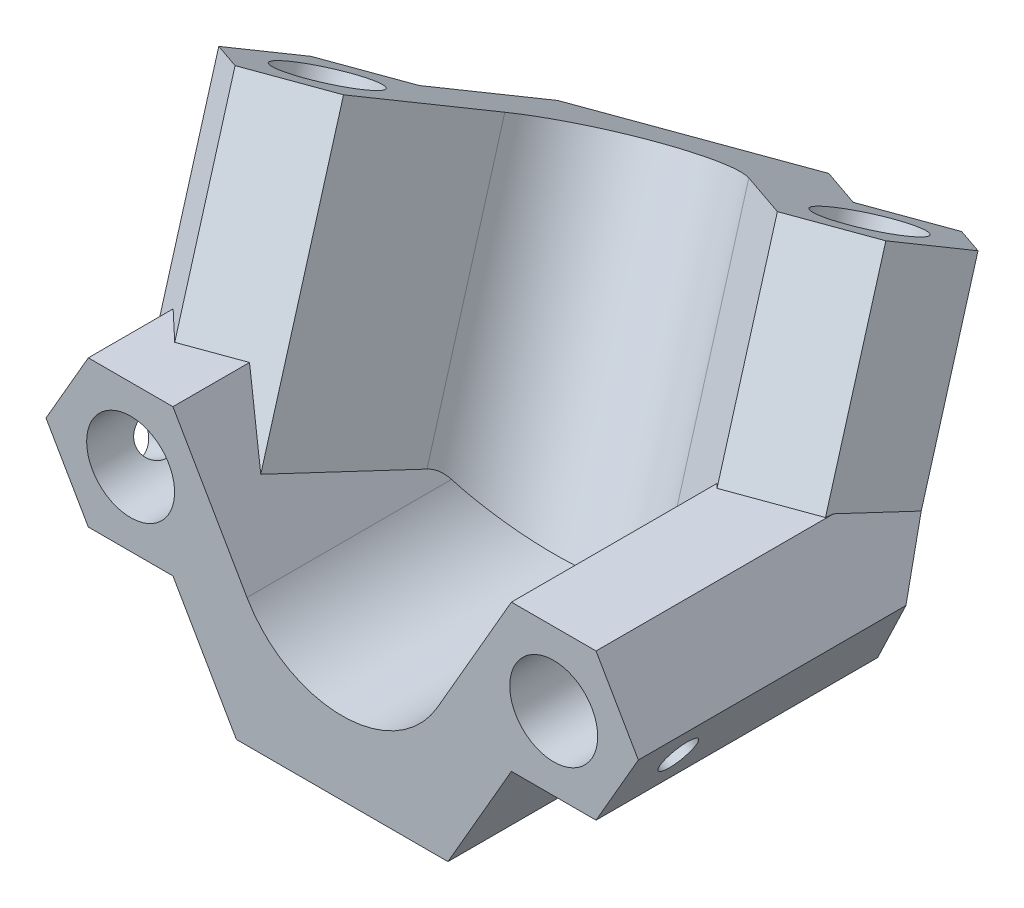
SolidWorks part; units mm, degrees
ref_plane "Front Plane" through (0, 0, 0) normal (0, 0, 1) x (1, 0, 0)
ref_plane "Top Plane" through (0, 0, 0) normal (0, 1, 0) x (1, 0, 0)
ref_plane "Right Plane" through (0, 0, 0) normal (1, 0, 0) x (0, 0, -1)
sketch "Sketch1" plane through (0, 0, 0) normal (0, 1, 0) x (1, 0, 0)
  line L0 (0, 0) -> (0, -10) construction
  line L1 (0, 0) -> (-3.4202, 9.3969) construction
  dimension "D1" = 10
  dimension "D2" = 160
  dimension "D3" = 10
ref_plane "Plane1" through (0, 0, 0) normal (0.9397, 0, -0.342) x (-0.342, 0, -0.9397)
sketch "Sketch2" plane through (0, 0, 0) normal (0.9397, 0, -0.342) x (-0.342, 0, -0.9397)
  line L0 (0, 0) -> (10, 0) construction
  line L1 (0, 0) -> (10, 0) construction
  line L2 (10, 0) -> (10, 17.3205) construction
  line L3 (10, 17.3205) -> (0, 0) construction
  dimension "D1" = 60
  dimension "D2" = 10
sketch "Sketch3" plane through (0, 0, 0) normal (0, 0, 1) x (1, 0, 0)
  line L0 (0, 15) -> (0, -15) construction
  line L1 (13.8564, 6) -> (8.6603, 15) construction
  line L2 (8.6603, 15) -> (0, 15) construction
  line L3 (-8.6603, 15) -> (-13.8564, 6) construction
  line L4 (-13.8564, -6) -> (-8.6603, -15)
  line L5 (-8.6603, -15) -> (8.6603, -15)
  line L6 (8.6603, -15) -> (13.8564, -6)
  line L7 (0, 0) -> (17.3205, 0) construction
  line L8 (13.8564, 6) -> (12.1244, 3) construction
  line L9 (24.2487, 0) -> (20.7846, 6)
  line L10 (20.7846, 6) -> (13.8564, 6)
  line L11 (12.1244, 3) -> (7.7942, -4.5) construction
  line L12 (12.1244, -3) -> (13.8564, -6) construction
  line L13 (13.8564, -6) -> (20.7846, -6)
  line L14 (20.7846, -6) -> (24.2487, 0)
  line L15 (10.3923, 0) -> (12.1244, -3) construction
  line L16 (13.8564, -6) -> (14.3205, -5.1962) construction
  line L17 (15.5205, -3.1177) -> (17.3205, 0) construction
  line L18 (14.3205, -5.1962) -> (15.5205, -3.1177) construction
  line L19 (17.3205, 0) -> (15.5205, 3.1177) construction
  line L20 (15.5205, 3.1177) -> (14.3205, 5.1962) construction
  line L21 (14.3205, 5.1962) -> (13.8564, 6) construction
  line L22 (-13.8564, -6) -> (-20.7846, -6)
  line L23 (-20.7846, -6) -> (-24.2487, 0)
  line L24 (-24.2487, 0) -> (-20.7846, 6)
  line L25 (-20.7846, 6) -> (-13.8564, 6)
  line L26 (-13.8564, 6) -> (-15.5205, 3.1177) construction
  line L27 (-15.5205, 3.1177) -> (-17.3205, 0) construction
  line L28 (-17.3205, 0) -> (-15.5205, -3.1177) construction
  line L29 (-15.5205, -3.1177) -> (-13.8564, -6) construction
  line L30 (-17.3205, 6) -> (-17.3205, -6) construction
  line L31 (-7.7942, -4.5) -> (-13.8564, 6)
  line L32 (7.7942, -4.5) -> (13.8564, 6)
  line L33 (-10.3923, 0) -> (-7.7942, -4.5) construction
  line L34 (0, 15) -> (-8.6603, 15) construction
  line L35 (7.7942, -4.5) -> (10.3923, 0) construction
  line L36 (10.3923, 0) -> (7.7942, -4.5) construction
  circle A0 centre (0, 0) radius 15 construction
  circle A1 centre (17.3205, 0) radius 3.6
  circle A2 centre (17.3205, 0) radius 6 construction
  circle A3 centre (-17.3205, 0) radius 3.6
  arc A4 (-7.7942, -4.5) -> (7.7942, -4.5) centre (0, 0) ccw
  arc A5 (0, 9) -> (-7.7942, -4.5) centre (0, 0) ccw construction
  arc A6 (7.7942, -4.5) -> (0, 9) centre (0, 0) ccw construction
  dimension "D2" = 7.2
  dimension "D4" = 18
  dimension "D1" = 30
  dimension "D3" = 12
extrude "Boss-Extrude1" add sketch "Sketch3" along normal blind 15
ref_plane "Plane2" through (-3.4202, 17.3205, -9.3969) normal (0.171, -0.866, 0.4698) x (-0.9849, -0.1641, 0.056)
sketch "Sketch25" plane through (0, 0, 0) normal (0, 0, -1) x (-1, 0, 0)
  line L0 (-7.7942, -4.5) -> (-13.8564, 6)
  line L1 (-13.8564, 6) -> (-20.7846, 6)
  line L2 (-20.7846, 6) -> (-24.2487, 0)
  line L3 (-24.2487, 0) -> (-20.7846, -6)
  line L4 (-20.7846, -6) -> (-13.8564, -6)
  line L5 (-13.8564, -6) -> (-8.6603, -15)
  line L6 (-8.6603, -15) -> (8.6603, -15)
  line L7 (8.6603, -15) -> (13.8564, -6)
  line L8 (13.8564, -6) -> (20.7846, -6)
  line L9 (20.7846, -6) -> (24.2487, 0)
  line L10 (24.2487, 0) -> (20.7846, 6)
  line L11 (20.7846, 6) -> (13.8564, 6)
  line L12 (13.8564, 6) -> (7.7942, -4.5)
  arc A0 (-7.7942, -4.5) -> (7.7942, -4.5) centre (0, 0) ccw
  arc A1 (-7.7942, -4.5) -> (7.7942, -4.5) centre (0, 0) ccw construction
  arc A2 (7.7942, -4.5) -> (-7.7942, -4.5) centre (0, 0) ccw construction
sketch "Sketch11" plane through (-3.4202, 17.3205, -9.3969) normal (0.171, -0.866, 0.4698) x (-0.9849, -0.1641, 0.056)
  line L0 (-4.9224, -14.1693) -> (4.9224, 14.1693) construction
  line L7 (13.1031, 11.3274) -> (-3.2583, 17.0113)
  line L20 (-3.2583, 17.0113) -> (-11.1201, 10.2148)
  line L21 (-15.058, -1.1206) -> (-13.1031, -11.3274) construction
  line L22 (-4.9224, -14.1693) -> (3.2583, -17.0113) construction
  line L23 (3.2583, -17.0113) -> (11.1201, -10.2148) construction
  line L24 (16.3613, -5.6839) -> (15.7029, -2.2464) construction
  line L25 (2.8419, 8.1807) -> (0, 0) construction
  line L26 (-16.3613, 5.6839) -> (16.3613, -5.6839) construction
  line L27 (15.058, 1.1206) -> (12.4374, -1.1449) construction
  line L28 (-11.1201, 10.2148) -> (-17.6647, 12.4884)
  line L35 (-17.6647, 12.4884) -> (-22.9059, 7.9574)
  line L42 (-22.9059, 7.9574) -> (-21.6026, 1.1529)
  line L43 (-21.6026, 1.1529) -> (-15.058, -1.1206)
  line L44 (-15.058, -1.1206) -> (-5.8859, 6.8085)
  line L45 (-8.8393, -1.6931) -> (-10.4685, 6.8126) construction
  line L46 (22.9059, -7.9574) -> (21.6026, -1.1529)
  line L47 (21.6026, -1.1529) -> (15.058, 1.1206)
  line L48 (5.8859, -6.8085) -> (9.8168, -3.4103) construction
  line L49 (8.8393, 1.6931) -> (11.1201, -10.2148)
  line L50 (11.1201, -10.2148) -> (17.6647, -12.4884)
  line L51 (17.6647, -12.4884) -> (22.9059, -7.9574)
  line L52 (12.4374, -1.1449) -> (5.8859, -6.8085) construction
  line L53 (9.8168, -3.4103) -> (8.8393, 1.6931) construction
  line L54 (15.2326, 0.209) -> (15.058, 1.1206) construction
  line L55 (15.058, 1.1206) -> (13.1031, 11.3274)
  line L56 (15.7029, -2.2464) -> (15.2326, 0.209) construction
  line L57 (13.7136, -7.9728) -> (16.3613, -5.6839) construction
  line L58 (11.8223, -9.6078) -> (13.7136, -7.9728) construction
  line L59 (11.1201, -10.2148) -> (11.8223, -9.6078) construction
  line L60 (-10.4685, 6.8126) -> (-11.1201, 10.2148) construction
  line L61 (-11.8223, 9.6078) -> (-13.6379, 8.0382) construction
  line L62 (-13.6379, 8.0382) -> (-16.3613, 5.6839) construction
  line L63 (-16.3613, 5.6839) -> (-15.6841, 2.1482) construction
  line L64 (-11.1201, 10.2148) -> (-11.8223, 9.6078) construction
  line L65 (-15.6841, 2.1482) -> (-15.2326, -0.209) construction
  line L66 (-15.2326, -0.209) -> (-15.058, -1.1206) construction
  line L67 (-5.8859, 6.8085) -> (-9.8168, 3.4103) construction
  line L68 (-9.8168, 3.4103) -> (-8.8393, -1.6931) construction
  line L69 (-13.1031, -11.3274) -> (-4.9224, -14.1693) construction
  circle A0 centre (0, 0) radius 15 construction
  circle A2 centre (-16.3613, 5.6839) radius 6 construction
  circle A4 centre (-16.3613, 5.6839) radius 3.6
  circle A5 centre (16.3613, -5.6839) radius 6 construction
  circle A6 centre (16.3613, -5.6839) radius 3.5
  arc A7 (8.8393, 1.6931) -> (-5.8859, 6.8085) centre (0, 0) ccw
  arc A8 (-2.9534, -8.5016) -> (8.8393, 1.6931) centre (0, 0) ccw construction
  arc A9 (-5.8859, 6.8085) -> (-2.9534, -8.5016) centre (0, 0) ccw construction
  dimension "D2" = 12
  dimension "D4" = 12
  dimension "D3" = 7.2
  dimension "D5" = 7
  dimension "D6" = 18
  dimension "D1" = 30
extrude "Boss-Extrude6" add sketch "Sketch11" along normal up to surface (33.8564 mm away) up to face at (0, -15, 7.5)
sketch "Sketch22" plane through (0, 0, 15) normal (0, 0, 1) x (1, 0, 0)
  line L0 (8.6603, -15) -> (-7.1843, -15)
  line L1 (-9.2861, -6.9129) -> (-7.1843, -15) construction
  circle A0 centre (-17.3205, 0) radius 3.6
  arc A1 (-15.6091, -3.1672) -> (-17.8643, 3.5587) centre (-17.3205, 0) ccw construction
  circle A2 centre (17.3205, 0) radius 3.6
  circle A3 centre (17.3205, 0) radius 3.6 construction
  circle A4 centre (0, 0) radius 9
  arc A5 (-7.7942, -4.5) -> (7.7942, -4.5) centre (0, 0) ccw construction
  arc M23 (7.7942, -4.5) -> (-7.7942, -4.5) centre (0, 0) cw
extrude "Cut-Extrude5" cut sketch "Sketch22" against normal up to surface (15 mm away) contours A4 M23 | A0 | A2 region at (0, 0, 15) up to face at (-19.4691, -1.9575, 0)
sketch "Sketch23" plane through (0, 0, 0) normal (0, 1, 0) x (1, 0, 0)
  line L0 (24.2487, -15) -> (24.2487, 0) construction
  line L1 (-24.2487, -15) -> (24.2487, -15)
  line L2 (-24.2487, -15) -> (-24.2487, -21.7571)
  line L3 (-24.2487, -21.7571) -> (24.2487, -21.7571)
  line L4 (24.2487, -15) -> (24.2487, -21.7571)
extrude "Cut-Extrude6" cut sketch "Sketch23" against normal through all both and the other way through all
sketch "Sketch24" plane through (0, 0, 15) normal (0, 0, 1) x (1, 0, 0)
  line L0 (-24.2487, 0) -> (-20.7846, -6)
  line L1 (-20.7846, -6) -> (-13.8564, -6)
  line L2 (-13.8564, -6) -> (-8.6603, -15)
  line L3 (-8.6603, -15) -> (-19.6596, -15)
  line L4 (-19.6596, -15) -> (-24.2487, 0)
  line L5 (8.6603, -15) -> (13.8564, -6)
  line L6 (13.8564, -6) -> (20.7846, -6)
  line L7 (20.7846, -6) -> (24.2487, 0)
  line L8 (24.2487, 0) -> (25.7483, -15)
  line L9 (25.7483, -15) -> (8.6603, -15)
extrude "Cut-Extrude7" cut sketch "Sketch24" against normal through all both and the other way through all
extrude "Boss-Extrude7" add sketch "Sketch25" along normal up to surface (18.5042 mm away) up to face at (-6.3157, -3.7874, -13.8064)
sketch "Sketch26" plane through (-3.4202, 17.3205, -9.3969) normal (-0.171, 0.866, -0.4698) x (0.9853, 0.1503, -0.0815)
  line L0 (-12.769, 11.7026) -> (-15.0192, 1.5568)
  line L1 (-15.0192, 1.5568) -> (-24.01, -1.2771)
  line L2 (-25.1148, -13.1846) -> (-23.1081, 8.4437) construction
  line L3 (-24.01, -1.2771) -> (-23.1081, 8.4437)
  line L4 (-23.1081, 8.4437) -> (-12.769, 11.7026)
  line L5 (3.7502, 16.9096) -> (11.4117, 9.8881)
  line L6 (11.4117, 9.8881) -> (18.0194, 11.9709)
  line L7 (18.0194, 11.9709) -> (24.4549, 6.0728)
  line L8 (22.6683, -13.1846) -> (26.1144, 23.959) construction
  line L9 (24.4549, 6.0728) -> (26.1144, 23.959)
  line L10 (26.1144, 23.959) -> (3.7502, 16.9096)
extrude "Cut-Extrude8" cut sketch "Sketch26" against normal through all both and the other way through all
sketch "Sketch27" plane through (-18.1865, -10.5, 0) normal (-0.866, -0.5, 0) x (0, 0, 1)
  line L0 (15, 8.6603) -> (2.6658, 8.6603) construction
  line L1 (15, 12.1244) -> (15, 5.1962) construction
  line L2 (1.453, 12.1244) -> (3.8786, 5.1962) construction
  line L3 (10, 12.1244) -> (10, 5.1962) construction
  line L4 (15, 12.1244) -> (1.453, 12.1244) construction
  line L5 (15, 5.1962) -> (3.8786, 5.1962) construction
  circle A0 centre (10, 8.6603) radius 1.5
  dimension "D1" = 3
  dimension "D2" = 5
extrude "Cut-Extrude9" cut sketch "Sketch27" against normal up to surface and the other way through all up to face at (-17.3205, 0, 0.7511)
sketch "Sketch28" plane through (18.1865, -10.5, 0) normal (0.866, -0.5, 0) x (0, 0, -1)
  line L0 (-15, 8.6603) -> (7.4822, 8.6603) construction
  line L1 (-15, 5.1962) -> (-15, 12.1244) construction
  line L2 (8.0554, 5.1962) -> (6.909, 12.1244) construction
  circle A0 centre (-10, 8.6603) radius 1.5
  dimension "D1" = 3
  dimension "D2" = 5
extrude "Cut-Extrude10" cut sketch "Sketch28" against normal up to surface (2.7274 mm away) up to face at (20.9205, 0, 0)
sketch "Sketch29" plane through (-20.1998, -5.25, -2.3247) normal (-0.9619, -0.25, -0.1107) x (-0.1071, -0.0278, 0.9939)
  line L0 (-1.8237, 21.7181) -> (5.4703, 8.1224) construction
  line L1 (1.2289, 23.3557) -> (-4.8762, 20.0804) construction
  line L2 (1.2869, 8.5925) -> (9.6536, 7.6523) construction
  circle A0 centre (0.5401, 17.3121) radius 1.5
  dimension "D1" = 3
  dimension "D2" = 5
extrude "Cut-Extrude11" cut sketch "Sketch29" against normal up to surface (2.5726 mm away) contours A0 up to face at (-19.6962, 15.6515, -6.5494)
sketch "Sketch30" plane through (13.9797, -5.25, -14.765) normal (0.6657, -0.25, -0.7031) x (-0.7462, -0.223, -0.6272)
  line L0 (-3.8464, 21.4524) -> (-9.4928, -2.5305) construction
  line L1 (-0.4745, 20.6585) -> (-7.2183, 22.2463) construction
  line L2 (-9.1192, -2.9545) -> (-13.7614, 2.3146) construction
  circle A0 centre (-4.9923, 16.5855) radius 1.5
  dimension "D1" = 3
  dimension "D2" = 5
extrude "Cut-Extrude12" cut sketch "Sketch30" against normal up to surface (2.6593 mm away) up to face at (12.8558, 15.6038, -18.4852)
sketch "Sketch31" plane through (-4.443, -7.5, -12.207) normal (-0.2962, -0.5, -0.8138) x (-0.9551, 0.1551, 0.2524)
  line L0 (3.5809, 19.6768) -> (-1.5506, -8.5203) construction
  line L1 (12.1012, 18.1262) -> (-4.9394, 21.2274) construction
  line L2 (-10.0709, -6.9697) -> (4.4154, -9.606) construction
  line L3 (-1.2063, 7.3345) -> (0.2261, 15.2052)
  line L4 (0.2261, 15.2052) -> (5.1453, 14.31)
  line L5 (5.1453, 14.31) -> (3.7129, 6.4393)
  line L6 (3.7129, 6.4393) -> (-1.2063, 7.3345)
  point P8 (2.6857, 14.7576)
  dimension "D1" = 5
  dimension "D2" = 8
  dimension "D3" = 5
extrude "Boss-Extrude8" add sketch "Sketch31" along normal blind 7
sketch "Sketch32" plane through (2.3492, 0, -0.8551) normal (0.9397, 0, -0.342) x (-0.342, 0, -0.9397)
  line L0 (24.5526, -1.4737) -> (18.4904, 2.0263) construction
  line L3 (26.5526, 1.9904) -> (22.5526, -4.9378) construction
  line L4 (8.6603, -15) -> (22.9904, 9.8205) construction
  circle A0 centre (22.3875, -0.2237) radius 1.25
  dimension "D1" = 2.5
  dimension "D2" = 2.5
extrude "Cut-Extrude13" cut sketch "Sketch32" against normal through all
sketch "Sketch33" plane through (-4.443, -7.5, -12.207) normal (-0.2962, -0.5, -0.8138) x (-0.9551, 0.1551, 0.2524)
  line L0 (1.2533, 6.8869) -> (20.9683, 115.2197) construction
  line L1 (-1.2063, 7.3345) -> (3.7129, 6.4393) construction
  line L2 (12.1012, 18.1262) -> (-4.9394, 21.2274) construction
sketch "Sketch34" plane through (2.3492, 0, -0.8551) normal (0.9397, 0, -0.342) x (-0.342, 0, -0.9397)
  line L0 (20.3875, -3.6878) -> (24.3875, 3.2404) construction
  line L1 (22.5526, -4.9378) -> (16.4904, -1.4378) construction
  line L2 (26.5526, 1.9904) -> (20.4904, 5.4904) construction
  line L3 (26.5526, 1.9904) -> (24.3875, 3.2404)
  line L4 (22.5526, -4.9378) -> (26.5526, 1.9904)
  line L5 (22.5526, -4.9378) -> (20.3875, -3.6878)
  line L8 (23.5125, 1.7248) -> (20.4904, 5.4904)
  line L9 (20.4904, 5.4904) -> (24.3875, 3.2404)
  line L10 (20.3875, -3.6878) -> (16.4904, -1.4378)
  line L11 (16.4904, -1.4378) -> (21.2625, -2.1723)
  arc A0 (21.2625, -2.1723) -> (23.5125, 1.7248) centre (22.3875, -0.2237) ccw
  arc A1 (23.5125, 1.7248) -> (21.2625, -2.1723) centre (22.3875, -0.2237) ccw construction
  dimension "D1" = 4.5
extrude "Cut-Extrude16" cut sketch "Sketch34" against normal up to next contours L5 L10 L11 A0 L8 L9 L3 L4
